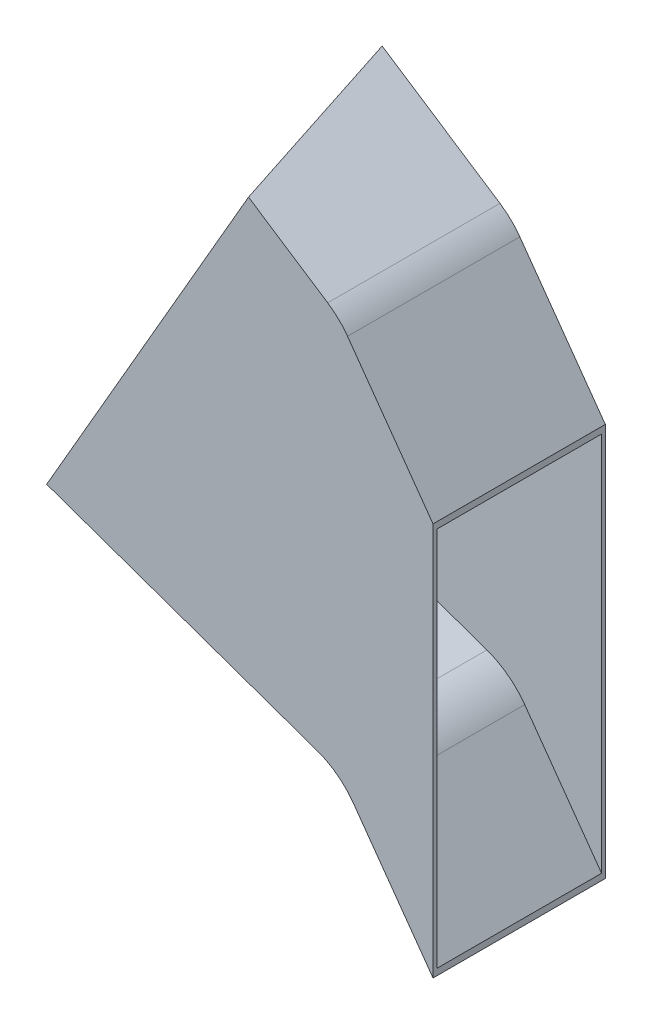
SolidWorks part; units mm, degrees
ref_plane "Front Plane" through (0, 0, 0) normal (0, 0, 1) x (1, 0, 0)
ref_plane "Top Plane" through (0, 0, 0) normal (0, 1, 0) x (1, 0, 0)
ref_plane "Right Plane" through (0, 0, 0) normal (1, 0, 0) x (0, 0, -1)
sketch "Sketch1" plane through (0, 0, 0) normal (0, 0, 1) x (1, 0, 0)
  line L0 (0, 0) -> (0, 266.7)
  line L1 (0, 266.7) -> (-63.5, 355.6)
  line L2 (-63.5, 355.6) -> (-152.4, 413.9682)
  line L3 (-152.4, 413.9682) -> (-279.4, 165.1)
  line L4 (-279.4, 165.1) -> (-63.5, 88.9)
  line L5 (-63.5, 88.9) -> (0, 0)
  point P5 (-225.5316, 439.2579)
  dimension "D1" = 63.5
  dimension "D2" = 266.7
  dimension "D3" = 88.9
  dimension "D4" = 215.9
  dimension "D5" = 76.2
  dimension "D6" = 279.4
  dimension "D7" = 127
extrude "Boss-Extrude1" add sketch "Sketch1" along normal blind 116.84
fillet "Fillet1" radius 50.8 2 edges at (-63.5, 355.6, 58.42) (-63.5, 88.9, 58.42)
shell "Shell2" thickness 2.54 removed face at (-215.9, 289.5341, 58.42) removed face at (0, 133.35, 58.42)
ref_plane "Plane1" through (0, 0, 0) normal (0.5, 0.866, 0) x (0, 0, -1)
sketch "Sketch8" plane through (0, 0, 0) normal (0.5, 0.866, 0) x (0, 0, -1)
  line L0 (0, 338.9664) -> (0, 337.6964)
  line L1 (0, 337.6964) -> (-116.84, 306.3892)
  line L2 (-116.84, 306.3892) -> (-116.84, 338.9664)
  line L3 (0, 242.2725) -> (0, 338.9664) construction
  line L4 (-116.84, 338.9664) -> (0, 338.9664)
  line L5 (-116.84, 242.2725) -> (-116.84, 338.9664) construction
  line L6 (-116.84, 338.9664) -> (0, 338.9664) construction
  point P4 (0, 0)
  point P7 (0, 0)
  point P12 (0, 330.3039)
  dimension "D1" = 15
  dimension "D2" = 1.27
extrude "Cut-Extrude7" cut sketch "Sketch8" against normal through all both and the other way through all
